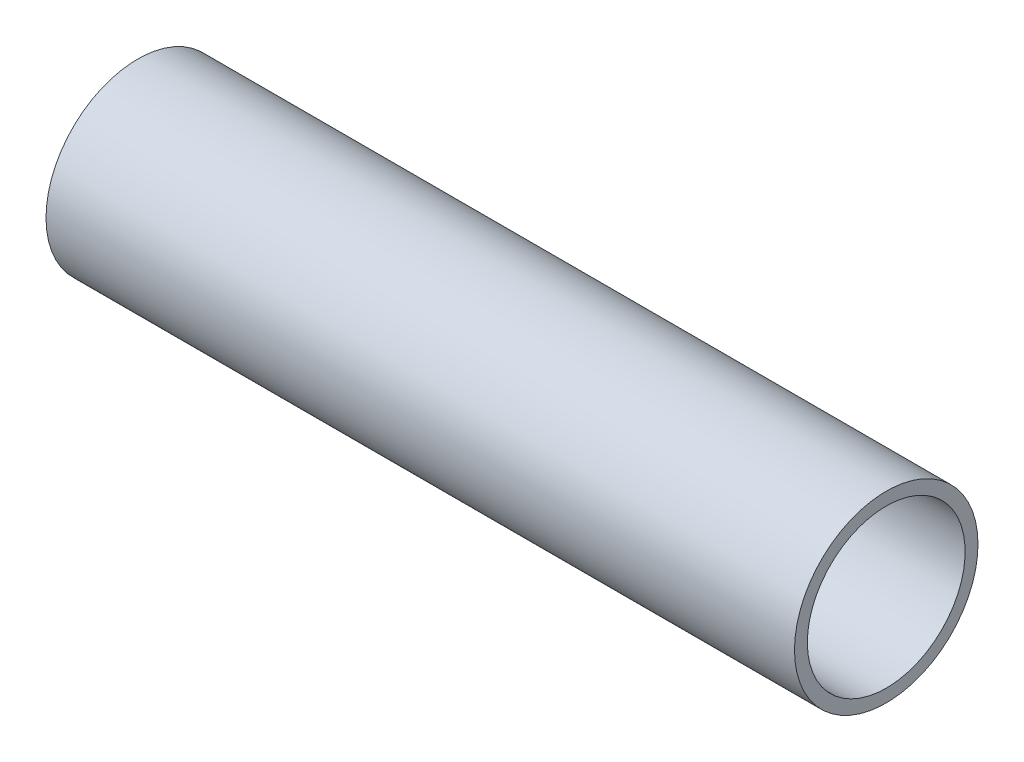
SolidWorks part; units mm, degrees
ref_plane "Front Plane" through (0, 0, 0) normal (0, 0, 1) x (1, 0, 0)
ref_plane "Top Plane" through (0, 0, 0) normal (0, 1, 0) x (1, 0, 0)
ref_plane "Right Plane" through (0, 0, 0) normal (1, 0, 0) x (0, 0, -1)
sketch "Tube_T8_Stub Sketch" plane through (0, 0, 0) normal (0, 0, 1) x (1, 0, 0)
  line L0 (-1000, 0) -> (1000, 0) construction
  line L1 (-25.9, 5.461) -> (-25.9, 6.35)
  line L2 (-25.9, 6.35) -> (25.9, 6.35)
  line L3 (25.9, 6.35) -> (25.9, 5.461)
  line L4 (25.9, 5.461) -> (-25.9, 5.461)
revolve "Tube_T8_Stub" add sketch "Tube_T8_Stub Sketch" angle 360 about L0
ref_axis "Engine Axis" through (28.49, 0, 0) along (-1, 0, 0)
